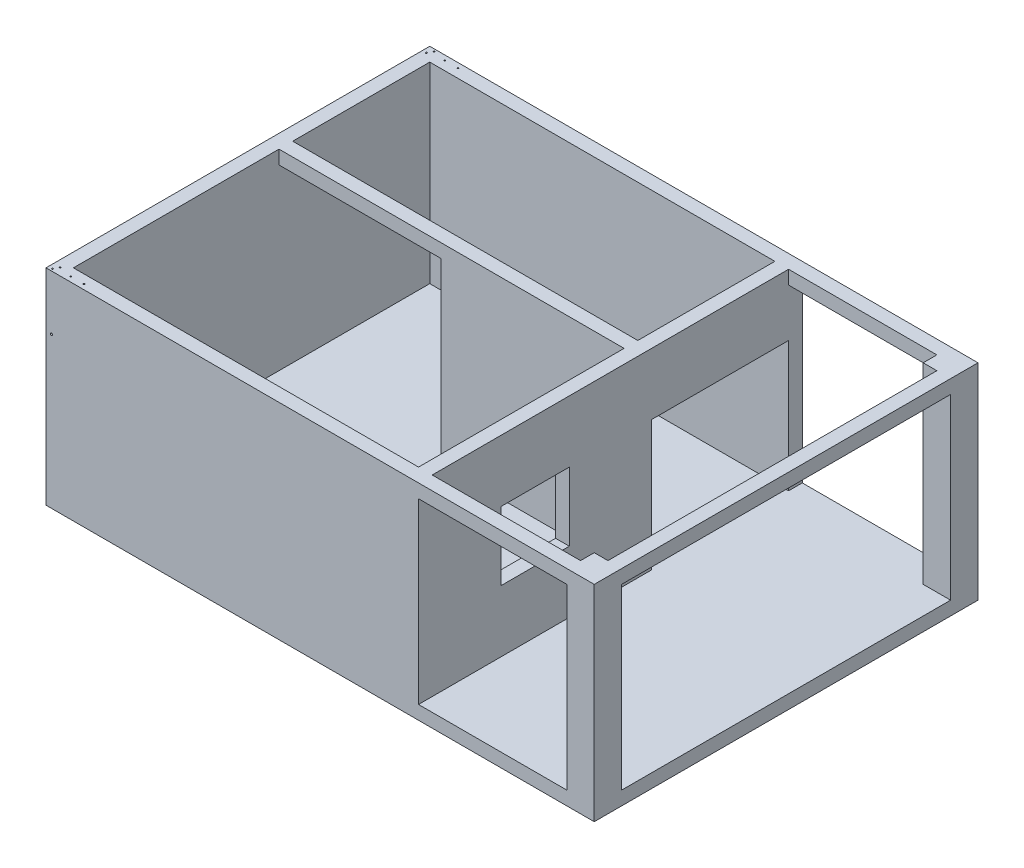
SolidWorks part; units mm, degrees
material "Pine"
ref_plane "Front Plane" through (0, 0, 0) normal (0, 0, 1) x (1, 0, 0)
ref_plane "Top Plane" through (0, 0, 0) normal (0, 1, 0) x (1, 0, 0)
ref_plane "Right Plane" through (0, 0, 0) normal (1, 0, 0) x (0, 0, -1)
sketch "Sketch1" plane through (0, 0, 0) normal (0, 1, 0) x (1, 0, 0)
  line L1 (0, 0) -> (2000, 0)
  line L2 (0, 0) -> (0, 1400)
  line L3 (0, 1400) -> (2000, 1400)
  line L4 (2000, 0) -> (2000, 1400)
  dimension "D1" = 2000
  dimension "D2" = 1400
extrude "Boss-Extrude1" add sketch "Sketch1" along normal blind 50
sketch "Sketch2" plane through (0, 50, 0) normal (0, 1, 0) x (1, 0, 0)
  line L0 (0, 700) -> (2000, 700) construction
  line L1 (2000, 1400) -> (1900, 1400)
  line L2 (2000, 1400) -> (2000, 1300)
  line L3 (2000, 1300) -> (1900, 1300)
  line L4 (1900, 1400) -> (1900, 1300)
  line L5 (0, 1400) -> (0, 0) construction
  line L6 (2000, 0) -> (2000, 1400) construction
  line L7 (2000, 100) -> (1900, 100)
  line L8 (1900, 0) -> (1900, 100)
  line L9 (2000, 0) -> (1900, 0)
  line L10 (2000, 0) -> (2000, 100)
  line L11 (0, 1350) -> (1359, 1350)
  line L12 (0, 0) -> (1359, 0)
  line L13 (0, 0) -> (0, 50)
  line L14 (0, 50) -> (1359, 50)
  line L15 (1359, 0) -> (1359, 50)
  line L16 (1359, 1400) -> (1359, 1350)
  line L17 (0, 1400) -> (1359, 1400)
  line L18 (0, 1400) -> (0, 1350)
  line L20 (0, 1350) -> (50, 1350)
  line L21 (0, 1350) -> (0, 50)
  line L22 (0, 50) -> (50, 50)
  line L23 (50, 1350) -> (50, 50)
  line L24 (641, 850) -> (1359, 850)
  line L25 (641, 850) -> (641, 800)
  line L26 (641, 800) -> (1359, 800)
  line L27 (1359, 850) -> (1359, 800)
  dimension "D1" = 100
  dimension "D2" = 100
  dimension "D3" = 1359
  dimension "D4" = 50
  dimension "D5" = 50
  dimension "D6" = 718
  dimension "D7" = 50
  dimension "D8" = 591
  dimension "D9" = 500
extrude "Boss-Extrude2" add sketch "Sketch2" along normal blind 700 contours L11 L16 L17 L18 | L21 L20 L23 L22 | L13 L12 L15 L14 | L25 L24 L27 L26 | L2 L1 L4 L3 | L7 L8 L9 L10
sketch "Sketch3" plane through (641, 0, 0) normal (-1, 0, 0) x (0, 0, 1)
  line L0 (-800, 750) -> (-800, 50) construction
  line L1 (-850, 750) -> (-800, 750)
  line L2 (-850, 750) -> (-850, 700)
  line L3 (-850, 700) -> (-800, 700)
  line L4 (-800, 750) -> (-800, 700)
  dimension "D1" = 50
extrude "Boss-Extrude3" add sketch "Sketch3" along normal up to surface (591 mm away) up to face at (50, 400, -700)
sketch "Sketch4" plane through (0, 50, 0) normal (0, 1, 0) x (1, 0, 0)
  line L0 (50, 50) -> (1359, 50) construction
  line L1 (1359, 800) -> (1309, 800)
  line L2 (1359, 800) -> (1359, 50)
  line L3 (1359, 50) -> (1309, 50)
  line L4 (1309, 800) -> (1309, 50)
  dimension "D1" = 50
extrude "Boss-Extrude4" add sketch "Sketch4" along normal up to vertex (700 mm away) up to point (1359, 750, -50)
sketch "Sketch5" plane through (1359, 0, 0) normal (1, 0, 0) x (0, 0, -1)
  line L1 (300, 525) -> (550, 525)
  line L2 (300, 525) -> (300, 275)
  line L3 (300, 275) -> (550, 275)
  line L4 (550, 525) -> (550, 275)
  line L5 (850, 750) -> (0, 750) construction
  line L6 (850, 750) -> (850, 50) construction
  dimension "D1" = 250
  dimension "D2" = 250
  dimension "D3" = 225
  dimension "D4" = 300
extrude "Cut-Extrude1" cut sketch "Sketch5" against normal blind 700
sketch "Sketch6" plane through (0, 0, -1350) normal (0, 0, 1) x (1, 0, 0)
  line L1 (1359, 750) -> (1309, 750)
  line L2 (1359, 750) -> (1359, 525)
  line L3 (1359, 525) -> (1309, 525)
  line L4 (1309, 750) -> (1309, 525)
  dimension "D1" = 225
  dimension "D2" = 50
extrude "Boss-Extrude5" add sketch "Sketch6" along normal up to surface (500 mm away) up to face at (683.3333, 500, -850)
sketch "Sketch7" plane through (0, 525, 0) normal (0, -1, 0) x (1, 0, 0)
sketch "Sketch8" plane through (1359, 0, 0) normal (1, 0, 0) x (0, 0, -1)
  line L0 (700, 750) -> (700, 0) construction
  line L1 (0, 750) -> (50, 750)
  line L2 (0, 750) -> (0, 700)
  line L3 (0, 700) -> (50, 700)
  line L4 (50, 750) -> (50, 700)
  line L5 (1400, 750) -> (0, 750) construction
  line L6 (0, 0) -> (1400, 0) construction
  line L7 (1400, 700) -> (1350, 700)
  line L8 (1350, 750) -> (1350, 700)
  line L9 (1400, 750) -> (1350, 750)
  line L10 (1400, 750) -> (1400, 700)
  dimension "D1" = 50
  dimension "D2" = 50
extrude "Boss-Extrude6" add sketch "Sketch8" along direction (-1, 0, 0) on the side of the normal up to surface (541 mm away) contours L2 L1 L4 L3 | L7 L8 L9 L10 up to face at (1900, 400, -50)
sketch "Sketch9" plane through (0, 0, -1300) normal (0, 0, 1) x (1, 0, 0)
  line L1 (2000, 750) -> (1950, 750)
  line L2 (2000, 750) -> (2000, 700)
  line L3 (2000, 700) -> (1950, 700)
  line L4 (1950, 750) -> (1950, 700)
  dimension "D1" = 50
  dimension "D2" = 50
extrude "Boss-Extrude7" add sketch "Sketch9" along normal up to surface (1200 mm away) up to face at (1950, 400, -100)
sketch "Sketch10" plane through (0, 750, 0) normal (0, 1, 0) x (1, 0, 0)
  line L27 (0.007, 1400.0023) -> (135.624, 1389.3162)
  line L29 (-0.0259, 35.8312) -> (135.5911, 25.1452)
  line L30 (-0.0117, 26.8312) -> (-0.0259, 35.8312)
  line L31 (135.606, 15.7452) -> (135.6132, 11.1452)
  line L32 (135.6132, 11.1452) -> (0.0306, 0.0313)
  line L33 (0.0306, 0.0313) -> (0.0164, 9.0312)
  line L34 (0.0164, 9.0312) -> (-8.4836, 9.0178)
  line L35 (-8.4836, 9.0178) -> (-8.5117, 26.8178)
  line L45 (-8.5117, 26.8178) -> (-0.0117, 26.8312)
  line L46 (135.5911, 25.1452) -> (135.5984, 20.5452)
  line L47 (135.6132, 11.1452) -> (0.0306, 0.0313)
  line L48 (135.606, 15.7452) -> (135.6132, 11.1452)
  line L49 (135.5911, 25.1452) -> (135.5984, 20.5452)
  line L50 (-8.5117, 26.8178) -> (-0.0117, 26.8312)
  line L51 (-8.4836, 9.0178) -> (-8.5117, 26.8178)
  line L52 (0.0164, 9.0312) -> (-8.4836, 9.0178)
  line L53 (0.0306, 0.0313) -> (0.0164, 9.0312)
  line L54 (0.0212, 1391.0023) -> (0.007, 1400.0023)
  line L55 (135.6388, 1379.9162) -> (135.6461, 1375.3162)
  line L56 (135.6461, 1375.3162) -> (0.0635, 1364.2023)
  line L57 (0.0635, 1364.2023) -> (0.0493, 1373.2023)
  line L58 (0.0493, 1373.2023) -> (-8.4507, 1373.1889)
  line L59 (-8.4507, 1373.1889) -> (-8.4788, 1390.9889)
  line L60 (-8.4788, 1390.9889) -> (0.0212, 1391.0023)
  line L61 (135.624, 1389.3162) -> (135.6313, 1384.7162)
  line L62 (135.6461, 1375.3162) -> (0.0635, 1364.2023)
  line L63 (135.6388, 1379.9162) -> (135.6461, 1375.3162)
  line L64 (135.624, 1389.3162) -> (135.6313, 1384.7162)
  line L65 (-8.4788, 1390.9889) -> (0.0212, 1391.0023)
  line L66 (-8.4507, 1373.1889) -> (-8.4788, 1390.9889)
  line L67 (0.0493, 1373.2023) -> (-8.4507, 1373.1889)
  line L68 (0.0635, 1364.2023) -> (0.0493, 1373.2023)
  arc A11 (135.5984, 20.5452) -> (135.606, 15.7452) centre (135.6022, 18.1452) cw
  circle A13 centre (14.6164, 9.0543) radius 2.764
  circle A14 centre (120.6022, 18.1215) radius 2.4
  circle A15 centre (72.6023, 18.0458) radius 2.4
  circle A16 centre (24.5883, 26.87) radius 2.515
  arc A17 (135.5984, 20.5452) -> (135.606, 15.7452) centre (135.6022, 18.1452) cw
  arc A18 (135.6313, 1384.7162) -> (135.6388, 1379.9162) centre (135.635, 1382.3162) cw
  circle A19 centre (14.6492, 1373.2253) radius 2.764
  circle A20 centre (120.6351, 1382.2926) radius 2.4
  circle A21 centre (72.6351, 1382.2168) radius 2.4
  circle A22 centre (24.6211, 1391.0411) radius 2.515
  arc A23 (135.6313, 1384.7162) -> (135.6388, 1379.9162) centre (135.635, 1382.3162) cw
extrude "Cut-Extrude2" cut sketch "Sketch10" against normal blind 10 contours A13 | A16 | A15 | A14 | A19 | A22 | A21 | A20
sketch "Sketch11" plane through (0, 0, 0) normal (0, 0, 1) x (1, 0, 0)
  line L0 (2000, 750) -> (0, 750) construction
  line L1 (0, 750) -> (0, 0) construction
  circle A0 centre (20, 550) radius 4
  dimension "D1" = 8
  dimension "D2" = 200
  dimension "D3" = 20
extrude "Cut-Extrude3" cut sketch "Sketch11" against normal through all both and the other way through all
